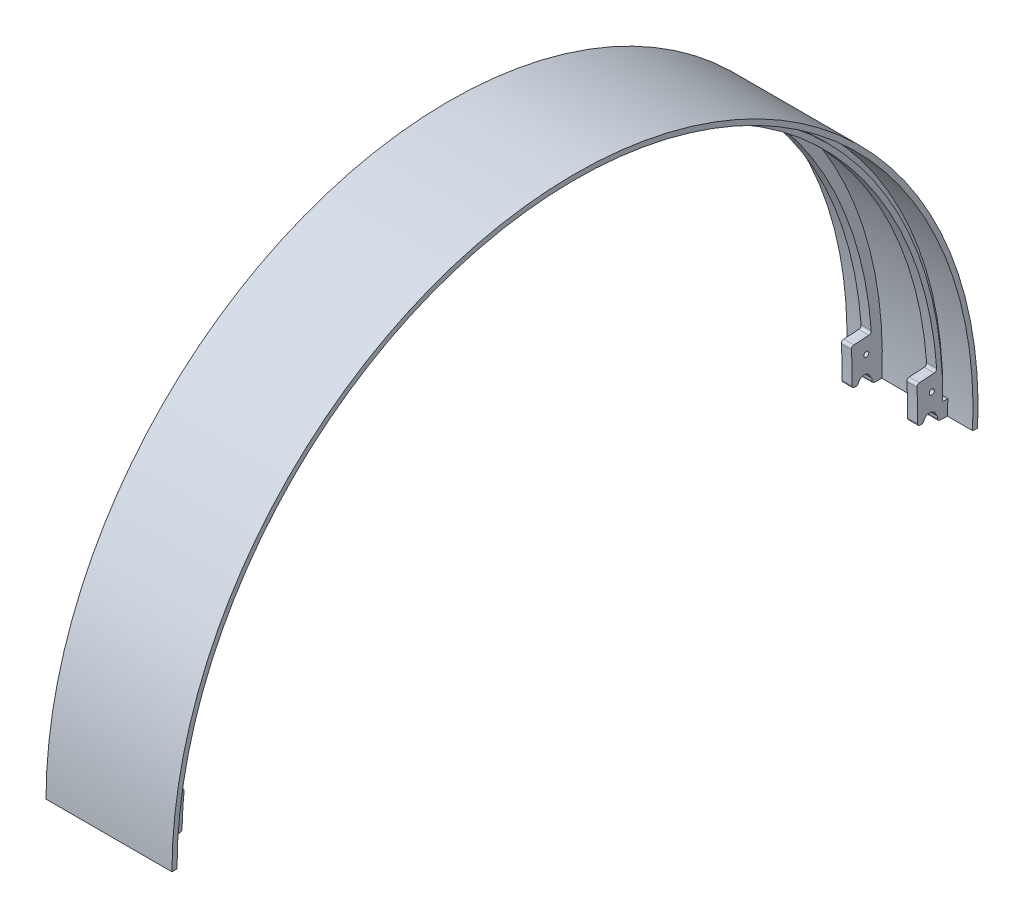
SolidWorks part; units mm, degrees
ref_plane "Alzado" through (0, 0, 0) normal (0, 0, 1) x (1, 0, 0)
ref_plane "Planta" through (0, 0, 0) normal (0, 1, 0) x (1, 0, 0)
ref_plane "Vista lateral" through (0, 0, 0) normal (1, 0, 0) x (0, 0, -1)
sketch "Croquis2" plane through (0, 0, 0) normal (0, 1, 0) x (1, 0, 0)
  line L0 (-22.133, 11.9975) -> (-22.133, 12.9975)
  line L1 (-22.133, 18.9975) -> (2.867, 18.9975)
  line L2 (-22.133, 18.9975) -> (-22.133, 11.9975)
  line L3 (-22.133, 11.9975) -> (2.867, 11.9975)
  line L4 (2.867, 18.9975) -> (2.867, 11.9975)
  line L5 (-22.133, 12.9975) -> (2.867, 12.9975)
  line L6 (2.867, 12.9975) -> (2.867, 11.9975)
  line L7 (-22.133, 12.9975) -> (-17.133, 12.9975)
  line L8 (-17.133, 12.9975) -> (-17.133, 18.9975)
  line L9 (-17.133, 18.9975) -> (-15.133, 18.9975)
  line L10 (-15.133, 18.9975) -> (-15.133, 12.9975)
  line L11 (-15.133, 12.9975) -> (-4.133, 12.9975)
  line L12 (-4.133, 12.9975) -> (-4.133, 18.9975)
  line L13 (-4.133, 18.9975) -> (-2.133, 18.9975)
  line L14 (-2.133, 18.9975) -> (-2.133, 12.9975)
  line L15 (-2.133, 12.9975) -> (2.867, 12.9975)
  line L16 (2.867, 12.9975) -> (2.7267, 13.2378)
  line L17 (-9.633, 11.9975) -> (-9.633, 91.9975)
  line L18 (-9.633, 91.9975) -> (-122.1314, 91.9975)
  dimension "D1" = 25
  dimension "D2" = 7
  dimension "D3" = 5
  dimension "D4" = 2
  dimension "D5" = 5
  dimension "D6" = 2
  dimension "D7" = 80
  dimension "D8" = 1
revolve "Revolución1" add sketch "Croquis2" angle 182.63 about L18
sketch "Croquis3" plane through (-2.133, 0, 0) normal (1, 0, 0) x (0, 0, -1)
  line L0 (91.9975, 0) -> (171.9132, -3.6713)
  line L1 (91.9975, 0) -> (11.9975, 0)
  line L2 (91.9975, 0) -> (171.9975, 5.3353)
  line L3 (91.9975, 0) -> (12.5032, 8.981)
  line L4 (91.9975, 0) -> (178.2878, -2.8838)
  line L5 (91.9975, 0) -> (-47.3575, 1.7433)
  line L6 (171.9132, -3.6713) -> (167.4179, -3.4648)
  line L7 (167.4179, -3.4648) -> (167.4179, -2.5206)
  line L8 (171.9132, -3.6713) -> (169.9177, -3.5796)
  line L9 (169.9177, -3.5796) -> (169.9503, -2.6052)
  line L10 (169.9503, -2.6052) -> (171.9132, -2.6708)
  line L11 (171.9132, -2.6708) -> (171.9132, -3.6713)
  line L12 (11.9975, 0) -> (16.4994, 0)
  line L13 (16.4994, 0) -> (16.5112, 0.9443)
  line L14 (11.9975, 0) -> (16.4994, 0)
  line L15 (16.5112, 0.9443) -> (12.0037, 1.0007)
  line L16 (12.0037, 1.0007) -> (11.9975, 0)
  line L17 (12.5032, 8.981) -> (16.4783, 8.5319)
  line L18 (16.4783, 8.5319) -> (16.4409, 5.5364)
  line L19 (171.9975, 5.3353) -> (167.8175, 5.0566)
  line L20 (167.8175, 5.0566) -> (167.8175, 2.0602)
  circle A0 centre (91.9975, 0) radius 62.4107
  circle A1 centre (91.9975, 0) radius 73
  circle A2 centre (91.9975, 0) radius 77
  circle A3 centre (167.4179, -2.5206) radius 1.25
  circle A4 centre (16.5112, 0.9443) radius 1.25
  arc A5 (171.9132, -3.6713) -> (11.9975, 0) centre (91.9975, 0) ccw construction
  circle A6 centre (16.4409, 5.5364) radius 0.5
  circle A8 centre (167.8175, 2.0602) radius 0.5
  dimension "D1" = 154
  dimension "D7" = 2.5
  dimension "D8" = 2.5
  dimension "D10" = 1
  dimension "D13" = 1
  dimension "D2" = 169.739
  dimension "D3" = 6.446
  dimension "D4" = 0.717
  dimension "D5" = 0.716
  dimension "D6" = 4.5
  dimension "D9" = 80
  dimension "D11" = 80
  dimension "D12" = 4.18
extrude "Cortar-Extruir2" cut sketch "Croquis3" against normal blind 64 and the other way blind 101
fillet "Redondeo1" radius 0.5 12 edges at (-3.133, -2.4788, -166.1686) (-3.133, -2.5623, -168.6672) (-16.133, -2.4788, -166.1686) (-16.133, -2.5623, -168.6672) (-3.133, 5.1239, -168.8268) (-16.133, 5.1239, -168.8268) (-16.133, -3.5336, -168.9164) (-3.133, -3.5336, -168.9164) (-3.133, -2.4383, -164.9567) (-16.133, -2.4383, -164.9567) (-16.133, 4.8577, -164.8357) (-3.133, 4.8577, -164.8357)
fillet "Redondeo2" radius 0.5 10 edges at (-3.133, 0.9287, -17.7612) (-16.133, 0.9287, -17.7612) (-3.133, 0.96, -15.2613) (-3.133, 0, -14.9975) (-16.133, 0, -14.9975) (-16.133, 0.96, -15.2613) (-3.133, 0.9131, -19.0032) (-3.133, 8.1952, -19.4589) (-3.133, 8.6442, -15.4842) (-16.133, 0.9131, -19.0032)
sketch "Croquis5" plane through (-2.133, 0, 0) normal (1, 0, 0) x (0, 0, -1)
  circle A0 centre (91.9975, 0) radius 79
  circle A1 centre (91.9975, 0) radius 78
  dimension "D1" = 156
extrude "Cortar-Extruir4" cut sketch "Croquis5" against normal blind 1
sketch "Croquis6" plane through (-17.133, 0, 0) normal (-1, 0, 0) x (0, 0, 1)
  circle A0 centre (-91.9975, 0) radius 79
  circle A1 centre (-91.9975, 0) radius 78
  dimension "D1" = 156
extrude "Cortar-Extruir5" cut sketch "Croquis6" against normal blind 1
sketch "Croquis7" plane through (0, 0, 0) normal (0, -1, 0) x (1, 0, 0)
  line L0 (-9.633, -11.9975) -> (-9.633, -91.9975)
  line L1 (-16.133, -12.9975) -> (-17.133, -12.9975)
  line L2 (-16.133, -12.9975) -> (-16.133, -13.9975)
  line L3 (-16.133, -13.9975) -> (-17.133, -13.9975)
  line L4 (-17.133, -12.9975) -> (-17.133, -13.9975)
  line L5 (-3.133, -12.9975) -> (-2.133, -12.9975)
  line L6 (-3.133, -12.9975) -> (-3.133, -13.9975)
  line L7 (-3.133, -13.9975) -> (-2.133, -13.9975)
  line L8 (-2.133, -12.9975) -> (-2.133, -13.9975)
  line L9 (-22.133, -11.9975) -> (2.867, -11.9975) construction
  line L10 (-9.633, -91.9975) -> (24.8428, -91.9975)
  dimension "D1" = 80
revolve "Revolución2" add sketch "Croquis7" angle 2.149 about L10
sketch "Croquis8" plane through (0, 4.2174, -0.1937) normal (0, -0.9989, 0.0459) x (1, 0, 0)
  line L2 (-17.133, -169.9006) -> (-16.133, -169.9006)
  line L3 (-17.133, -169.9006) -> (-17.133, -170.9006)
  line L4 (-17.133, -170.9006) -> (-16.133, -170.9006)
  line L5 (-3.133, -170.9006) -> (2.867, -170.9006) construction
  line L6 (-3.133, -169.9006) -> (-2.133, -169.9006)
  line L7 (-3.133, -169.9006) -> (-3.133, -170.9006)
  line L8 (-3.133, -170.9006) -> (-2.133, -170.9006)
  line L9 (-2.133, -169.9006) -> (-2.133, -170.9006)
  line L10 (-9.633, -171.9006) -> (-9.633, -91.9006)
  line L11 (-22.133, -171.9006) -> (2.867, -171.9006) construction
  line L12 (-9.633, -91.9006) -> (-47.874, -91.9006)
  line L13 (-16.133, -169.9006) -> (-16.133, -170.9006)
  dimension "D1" = 80
revolve "Revolución4" add sketch "Croquis8" angle 2.15 about L12
